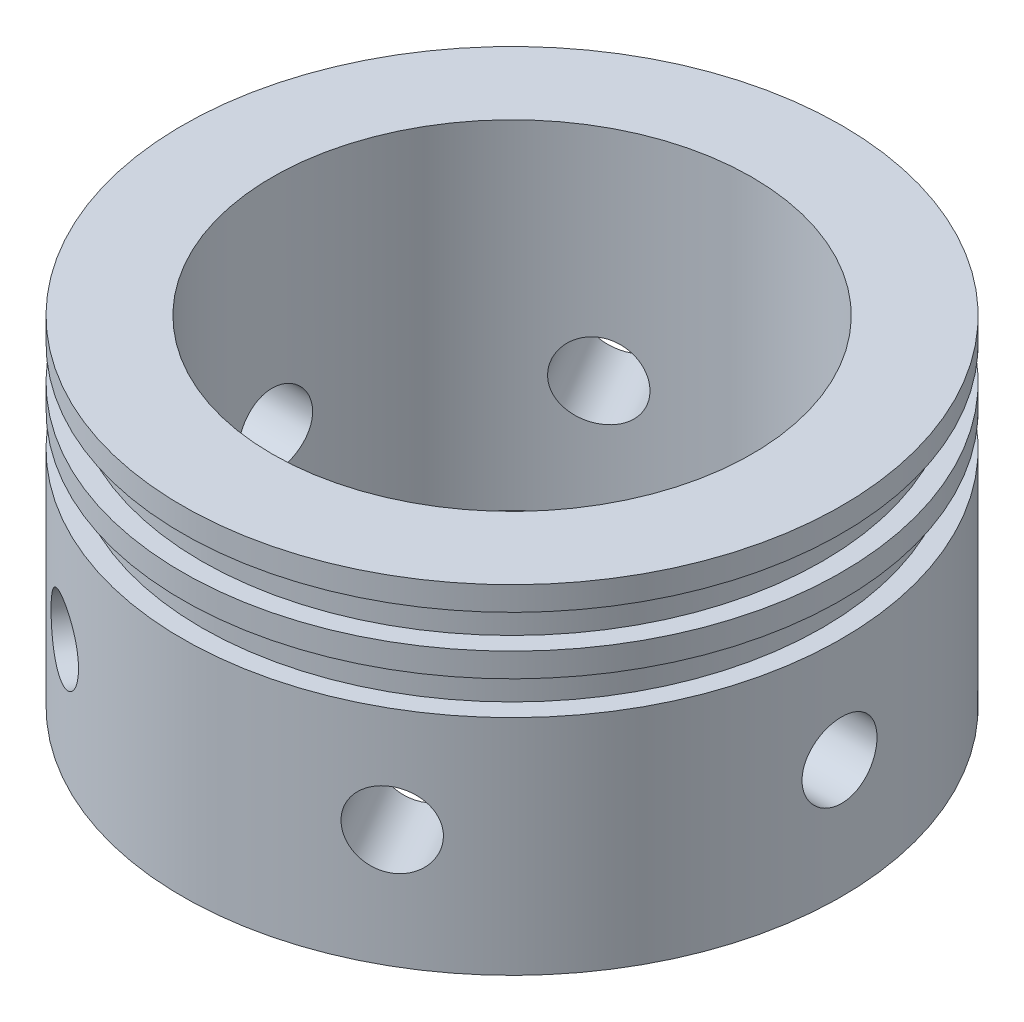
SolidWorks part; units mm, degrees
material "6061-T6 (SS)"
ref_plane "Front Plane" through (0, 0, 0) normal (0, 0, 1) x (1, 0, 0)
ref_plane "Top Plane" through (0, 0, 0) normal (0, 1, 0) x (1, 0, 0)
ref_plane "Right Plane" through (0, 0, 0) normal (1, 0, 0) x (0, 0, -1)
sketch "Sketch2" plane through (0, 0, 0) normal (0, 0, 1) x (1, 0, 0)
  line L0 (0, 0) -> (0, 56.8921) construction
  line L1 (-34.8996, 40.6893) -> (-25.4, 40.6893)
  line L2 (-34.8996, 40.6893) -> (-34.8996, 38.1493)
  line L3 (-34.8996, 4.8576) -> (-25.4, 4.8576)
  line L4 (-25.4, 40.6893) -> (-25.4, 4.8576)
  line L5 (-34.8996, 38.1493) -> (-32.8676, 38.1493)
  line L6 (-32.8676, 38.1493) -> (-32.8676, 34.5933)
  line L7 (-32.8676, 34.5933) -> (-34.8996, 34.5933)
  line L8 (-34.8996, 32.0533) -> (-32.8676, 32.0533)
  line L9 (-32.8676, 32.0533) -> (-32.8676, 28.4973)
  line L10 (-32.8676, 28.4973) -> (-34.8996, 28.4973)
  line L12 (-34.8996, 34.5933) -> (-34.8996, 32.0533)
  line L13 (-34.8996, 28.4973) -> (-34.8996, 4.8576)
  point P15 (-32.8676, 30.2753)
  dimension "D1" = 34.8996
  dimension "D2" = 25.4
  dimension "D3" = 35.8317
  dimension "D4" = 3.556
  dimension "D5" = 3.556
  dimension "D6" = 2.032
  dimension "D7" = 2.032
  dimension "D8" = 2.54
  dimension "D9" = 2.54
revolve "Revolve1" add sketch "Sketch2" angle 360 about L0
ref_plane "Plane1" through (34.8996, 0, 0) normal (1, 0, 0) x (0, 0, -1)
sketch "Sketch5" plane through (34.8996, 0, 0) normal (1, 0, 0) x (0, 0, -1)
  line L0 (25.4, 40.6893) -> (-25.4, 40.6893) construction
  point P0 (0, 21.0043)
  point P1 (0, 0)
  point P2 (0, 21.0043)
  dimension "D1" = 19.685
hole_wizard "3/8-16 Tapped Hole2" positions "Sketch11" profile "Sketch12" tap size "3/8-16" standard "ANSI Inch" end condition up to next
sketch "Sketch11" plane through (34.8996, 0, 0) normal (1, 0, 0) x (0, 0, -1)
  line L0 (0, 0) -> (0, 49.9183) construction
  line L3 (-34.8996, 4.8576) -> (34.8996, 4.8576) construction
  point P0 (0, 17.3721)
  dimension "D1" = 12.5145
sketch "Sketch12" plane through (34.8996, 17.3721, 0) normal (0, 1, 0) x (0, 0, -1)
  line L0 (0, 0) -> (0, 9.4996)
  line L1 (0, 9.4996) -> (3.9687, 9.4996)
  line L2 (3.9687, 9.4996) -> (3.9687, 0)
  line L5 (3.9687, 0) -> (0, 0)
  line L11 (0, -6.35) -> (0, 107.95) construction
  dimension "Thru Tap Drill Dia." = 7.9375
  dimension "Thru Tap Drill Depth" = 9.4996
cosmetic thread "Hole Thread4" parameters "D2"=9.525
ref_axis "Axis1" through (0, 40.6893, 0) along (0, -1, 0)
pattern_circular "CirPattern1" count 6 over 360 about axis through (0, 40.6893, 0) along (0, -1, 0) of "3/8-16 Tapped Hole2" reverse direction yes
cosmetic thread "Hole Thread5" parameters "D2"=9.525
cosmetic thread "Hole Thread6" parameters "D2"=9.525
cosmetic thread "Hole Thread7" parameters "D2"=9.525
cosmetic thread "Hole Thread8" parameters "D2"=9.525
cosmetic thread "Hole Thread9" parameters "D2"=9.525
ref_plane "Plane2" through (0, 0, 34.8996) normal (0, 0, 1) x (1, 0, 0)
